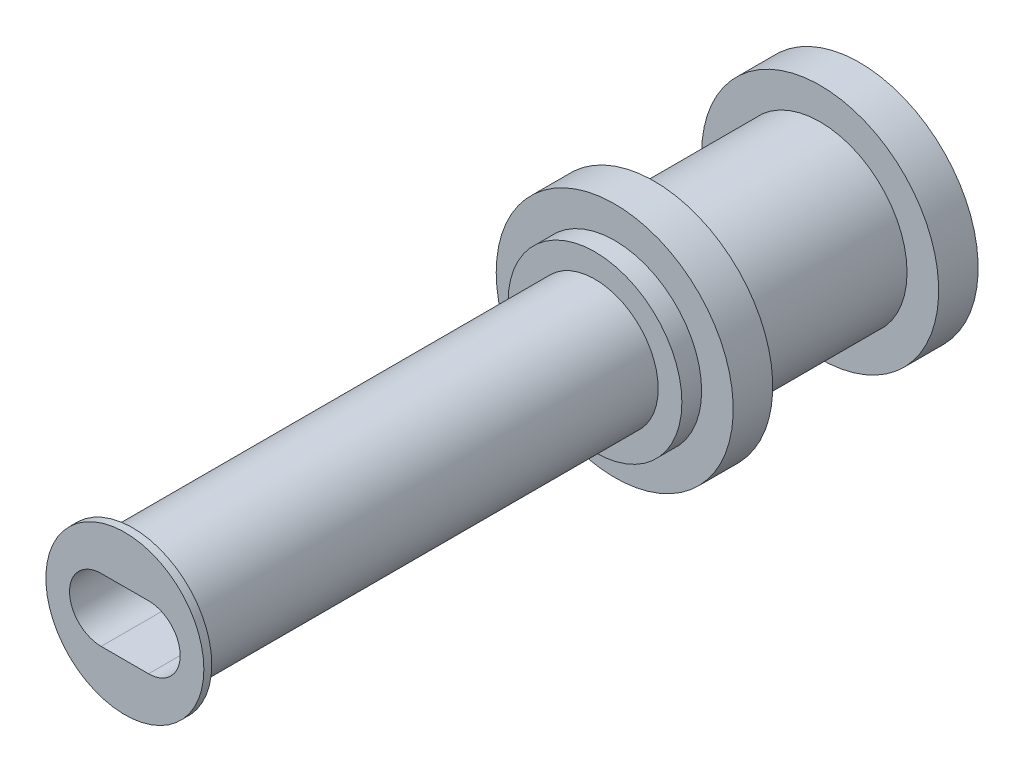
SolidWorks part; units mm, degrees
material "PVC Rigid"
ref_plane "Front Plane" through (0, 0, 0) normal (0, 0, 1) x (1, 0, 0)
ref_plane "Top Plane" through (0, 0, 0) normal (0, 1, 0) x (1, 0, 0)
ref_plane "Right Plane" through (0, 0, 0) normal (1, 0, 0) x (0, 0, -1)
sketch "Sketch1" plane through (0, 0, 0) normal (0, 0, 1) x (1, 0, 0)
  line L0 (-7.874, 0) -> (7.874, 0) construction
  line L1 (6.35, 0) -> (9.398, 0) construction
  line L2 (6.35, 0.762) -> (9.398, 0.762)
  line L10 (6.35, -0.762) -> (9.398, -0.762)
  line L19 (7.874, 1.524) -> (7.874, -1.524) construction
  line L20 (8.636, 1.524) -> (8.636, -1.524)
  line L21 (7.112, 1.524) -> (7.112, -1.524)
  line L22 (6.35, 0) -> (9.398, 0) construction
  circle A0 centre (7.874, 0) radius 2.794
  arc A2 (6.35, 0.762) -> (6.35, -0.762) centre (6.35, 0) ccw
  circle A4 centre (7.874, 0) radius 2.54
  arc A5 (9.398, -0.762) -> (9.398, 0.762) centre (9.398, 0) ccw
  circle A23 centre (7.874, 0) radius 2.286 construction
  arc A24 (8.636, 1.524) -> (7.112, 1.524) centre (7.874, 1.524) ccw
  arc A25 (7.112, -1.524) -> (8.636, -1.524) centre (7.874, -1.524) ccw
  point P13 (9.525, 0)
  point P14 (7.874, 0)
  point P15 (7.62, 0)
  point P17 (0, 3.302)
  point P18 (19.05, 3.302)
  point P19 (0, -3.302)
  point P20 (19.05, -3.302)
  point P23 (13.843, 0)
  point P24 (7.874, 0)
  point P25 (23.368, 0)
  point P26 (3.429, 0)
  point P27 (-7.874, -3.302)
  point P28 (7.874, -3.302)
  point P29 (-7.874, 3.302)
  point P30 (7.874, 3.302)
  point P35 (11.811, 0)
  point P60 (11.5175, 1.1139)
  point P70 (7.874, 0)
  point P77 (7.874, 0)
  dimension "D4" = 5.08
  dimension "D7" = 4.572
  dimension "D8" = 1.524
extrude "Boss-Extrude1" add sketch "Sketch1" along normal blind 3.937 contours A4 | L20 A25 L21 A4 A24 region at (5.159, 0, 0) region at (5.4058, 0, 0)
sketch "Sketch2" plane through (0, 0, 0) normal (0, 0, -1) x (-1, 0, 0)
  circle A0 centre (-7.874, 0) radius 2.794
  circle A1 centre (-7.874, 0) radius 3.81
extrude "Boss-Extrude2" add sketch "Sketch2" against normal blind 1.27
ref_plane "Plane1" through (0, 0, 3.937) normal (0, 0, 1) x (1, 0, 0)
mirror "Mirror1" about plane through (0, 0, 3.937) normal (0, 0, 1) of "Boss-Extrude2", "Boss-Extrude1"
sketch "Sketch3" plane through (0, 0, 7.874) normal (0, 0, 1) x (1, 0, 0)
  circle A0 centre (7.874, 0) radius 2.794
extrude "Boss-Extrude3" add sketch "Sketch3" along normal blind 0.635
sketch "Sketch4" plane through (0, 0, 8.509) normal (0, 0, 1) x (1, 0, 0)
  circle A0 centre (7.874, 0) radius 2.032
extrude "Boss-Extrude4" add sketch "Sketch4" along normal blind 15.113
sketch "Sketch5" plane through (0, 0, 23.622) normal (0, 0, 1) x (1, 0, 0)
  circle A0 centre (7.874, 0) radius 2.032
  circle A1 centre (7.874, 0) radius 2.54
extrude "Boss-Extrude5" add sketch "Sketch5" against normal blind 0.254
sketch "Sketch6" plane through (0, 0, 23.622) normal (0, 0, 1) x (1, 0, 0)
  line L0 (8.636, 0) -> (7.112, 0) construction
  line L1 (8.636, -1.016) -> (7.112, -1.016)
  line L2 (8.636, 1.016) -> (7.112, 1.016)
  arc A0 (8.636, -1.016) -> (8.636, 1.016) centre (8.636, 0) ccw
  arc A1 (7.112, 1.016) -> (7.112, -1.016) centre (7.112, 0) ccw
  point P3 (7.874, 0)
extrude "Cut-Extrude1" cut sketch "Sketch6" along direction (0, 0, 1) on the side against the normal blind 15.24
